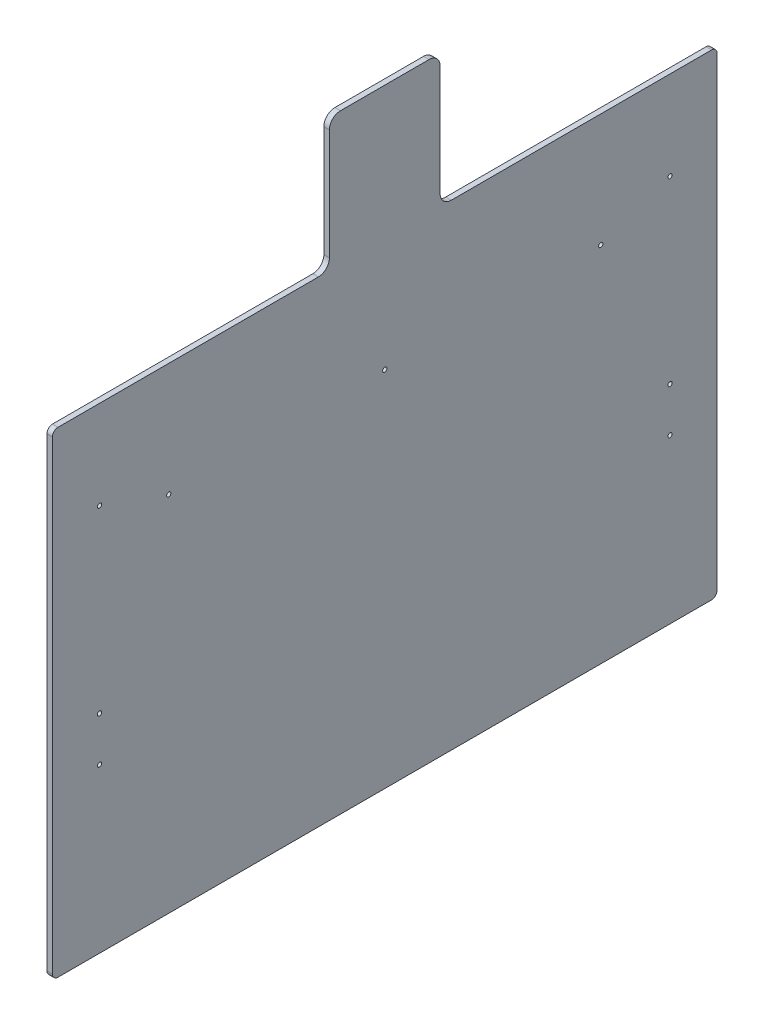
SolidWorks part; units mm, degrees
material "PE High Density"
ref_plane "Front Plane" through (0, 0, 0) normal (0, 0, 1) x (1, 0, 0)
ref_plane "Top Plane" through (0, 0, 0) normal (0, 1, 0) x (1, 0, 0)
ref_plane "Right Plane" through (0, 0, 0) normal (1, 0, 0) x (0, 0, -1)
sketch "Sketch1" plane through (0, 0, 0) normal (1, 0, 0) x (0, 0, -1)
  line L0 (457.2, 546.1) -> (755.65, 546.1)
  line L1 (6.35, 0) -> (755.65, 0)
  line L2 (0, 6.35) -> (0, 539.75)
  line L3 (6.35, 546.1) -> (304.8, 546.1)
  line L4 (762, 6.35) -> (762, 539.75)
  line L6 (317.5, 558.8) -> (317.5, 685.8)
  line L7 (330.2, 698.5) -> (431.8, 698.5)
  line L8 (444.5, 558.8) -> (444.5, 685.8)
  arc A0 (6.35, 0) -> (0, 6.35) centre (6.35, 6.35) cw
  arc A1 (755.65, 0) -> (762, 6.35) centre (755.65, 6.35) ccw
  arc A2 (755.65, 546.1) -> (762, 539.75) centre (755.65, 539.75) cw
  arc A3 (0, 539.75) -> (6.35, 546.1) centre (6.35, 539.75) cw
  circle A4 centre (53.975, 444.5) radius 2.4575
  circle A5 centre (708.025, 444.5) radius 2.4575
  circle A6 centre (708.025, 238.125) radius 2.4575
  circle A8 centre (53.975, 238.125) radius 2.4574
  circle A9 centre (53.975, 187.325) radius 2.4574
  circle A10 centre (708.025, 187.325) radius 2.4575
  arc A11 (304.8, 546.1) -> (317.5, 558.8) centre (304.8, 558.8) ccw
  arc A12 (457.2, 546.1) -> (444.5, 558.8) centre (457.2, 558.8) cw
  arc A13 (431.8, 698.5) -> (444.5, 685.8) centre (431.8, 685.8) cw
  arc A14 (317.5, 685.8) -> (330.2, 698.5) centre (330.2, 685.8) cw
  point P7 (0, 0)
  point P12 (762, 546.1)
  point P15 (0, 546.1)
  point P34 (317.5, 546.1)
  point P39 (444.5, 698.5)
  point P42 (317.5, 698.5)
  point P43 (0, 0)
  dimension "D3" = 6.35
  dimension "D6" = 4.9149
  dimension "D11" = 53.975
  dimension "D13" = 50.8
  dimension "D17" = 12.7
  dimension "D1" = 546.1
  dimension "D2" = 762
  dimension "D4" = 654.05
  dimension "D5" = 101.6
  dimension "D9" = 53.975
  dimension "D10" = 206.375
  dimension "D12" = 50.8
  dimension "D14" = 127
  dimension "D15" = 317.5
  dimension "D16" = 152.4
  dimension "D7" = 2
  dimension "D8" = 2
extrude "Boss-Extrude1" add sketch "Sketch1" along normal blind 6.35
sketch "Sketch3" plane through (6.35, 0, 0) normal (1, 0, 0) x (0, 0, -1)
  line L13 (304.8, 546.1) -> (6.35, 546.1) construction
  line L14 (0, 539.75) -> (0, 6.35) construction
  circle A2 centre (133.35, 415.925) radius 2.4575
  circle A3 centre (381, 415.925) radius 2.4574
  circle A4 centre (628.65, 415.925) radius 2.4575
  dimension "D2" = 130.175
  dimension "D12" = 4.9149
  dimension "D6" = 133.35
  dimension "D4" = 247.65
  dimension "D5" = 247.65
extrude "Cut-Extrude2" cut sketch "Sketch3" against normal through all
